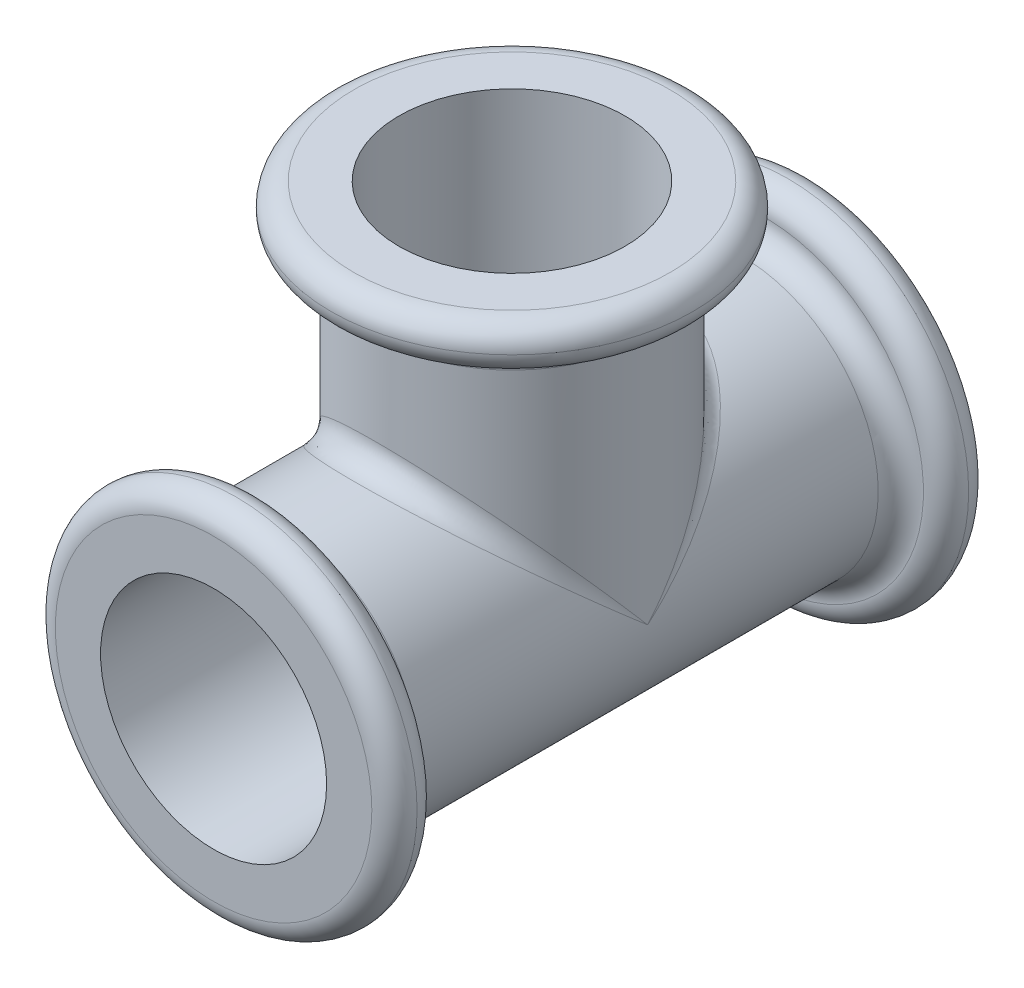
SolidWorks part; units mm, degrees
ref_plane "Front Plane" through (0, 0, 0) normal (0, 0, 1) x (1, 0, 0)
ref_plane "Top Plane" through (0, 0, 0) normal (0, 1, 0) x (1, 0, 0)
ref_plane "Right Plane" through (0, 0, 0) normal (1, 0, 0) x (0, 0, -1)
sketch "Sketch1" plane through (0, 0, 0) normal (0, 0, 1) x (1, 0, 0)
  circle A0 centre (0, 0) radius 12.5
  circle A1 centre (0, 0) radius 15
  dimension "D1" = 25
  dimension "D2" = 30
extrude "Boss-Extrude1" add sketch "Sketch1" along normal mid plane 56
ref_plane "Plane1" through (0, 30, 0) normal (0, 1, 0) x (1, 0, 0)
sketch "Sketch2" plane through (0, 30, 0) normal (0, 1, 0) x (1, 0, 0)
  circle A0 centre (0, 0) radius 12.5
  circle A1 centre (0, 0) radius 15
  dimension "D1" = 30
  dimension "D2" = 25
extrude "Boss-Extrude2" add sketch "Sketch2" against normal up to surface (15 mm away) up to face at (15, 0, 28)
sketch "Sketch3" plane through (0, 30, 0) normal (0, 1, 0) x (1, 0, 0)
  circle A0 centre (0, 0) radius 12.5
extrude "Cut-Extrude1" cut sketch "Sketch3" against normal blind 30
sketch "Sketch4" plane through (0, 0, 28) normal (0, 0, 1) x (1, 0, 0)
  circle A0 centre (0, 0) radius 20
  circle A1 centre (0, 0) radius 12.5
  dimension "D1" = 40
extrude "Boss-Extrude3" add sketch "Sketch4" along normal blind 5
ref_plane "Plane2" through (0, 0, 0) normal (0, 0, 1) x (1, 0, 0)
mirror "Mirror6" about plane through (0, 0, 0) normal (0, 0, 1) of "Boss-Extrude3"
fillet "Fillet3" radius 2.5 3 edges at (-15, 0, -28) (20, 0, -33) (20, 0, -28)
fillet "Fillet4" radius 2.5 3 edges at (20, 0, 33) (20, 0, 28) (15, 0, 28)
sketch "Sketch5" plane through (0, 30, 0) normal (0, 1, 0) x (1, 0, 0)
  circle A0 centre (0, 0) radius 20
  circle A1 centre (0, 0) radius 12.5
  dimension "D1" = 40
extrude "Boss-Extrude4" add sketch "Sketch5" along normal blind 5
fillet "Fillet5" radius 2.5 5 edges at (0, 15, -15) (0, 15, 15) (0, 30, 15) (0, 30, 20) (0, 35, 20)
